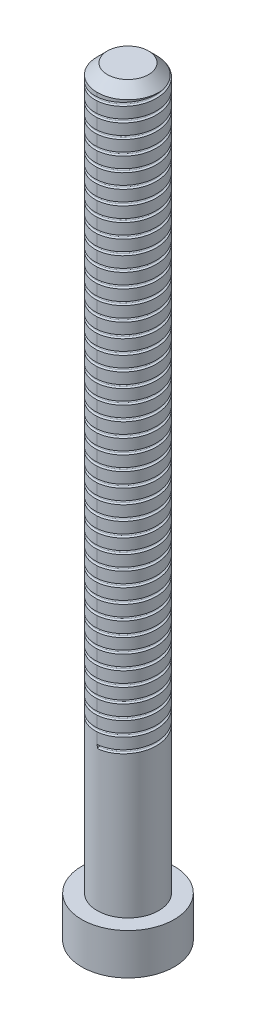
SolidWorks part; units mm, degrees
note: '?' marks a value the reader was unsure of.
ref_plane "Front Plane" through (0, 0, 0) normal (0, 0, 1) x (1, 0, 0)
ref_plane "Top Plane" through (0, 0, 0) normal (0, 1, 0) x (1, 0, 0)
ref_plane "Right Plane" through (0, 0, 0) normal (1, 0, 0) x (0, 0, -1)
sketch "Sketch1" plane through (0, 0, 0) normal (0, 1, 0) x (1, 0, 0)
  line L1 (2.5981, 0) -> (1.299, 2.25) construction
  line L2 (1.299, 2.25) -> (-1.299, 2.25) construction
  line L3 (-1.299, 2.25) -> (-2.5981, 0) construction
  line L4 (-2.5981, 0) -> (-1.299, -2.25) construction
  line L5 (-1.299, -2.25) -> (1.299, -2.25) construction
  line L6 (1.299, -2.25) -> (2.5981, 0) construction
  circle A0 centre (0, 0) radius 2.25
  dimension "D1" = 4.5
extrude "Boss-Extrude1" add sketch "Sketch1" along normal blind 37
sketch "Sketch2" plane through (0, 37, 0) normal (0, 1, 0) x (1, 0, 0)
  circle A0 centre (0, 0) radius 1.5
  dimension "D1" = 3
extrude "Cut-Extrude1" cut sketch "Sketch2" against normal blind 35 flip side to cut
ref_axis "Axis1" through (0, 2, 0) along (0, 1, 0)?
chamfer "Chamfer1" distance 0.5 angle 45 1 edges at (0, 37, 1.5)
sketch "Sketch5" plane through (0, 37, 0) normal (0, 1, 0) x (1, 0, 0)
  circle A0 centre (0, 0) radius 1.5
  dimension "D1" = 3
curve "Helix/Spiral1" pitch 0.7 height 28 turns 40
ref_plane "Plane1" through (0, 37, 1.5) normal (-0.9973, -0.0741, 0) x (0, 0, 1)
sketch "Sketch7" plane through (0, 37, 1.5) normal (-0.9973, -0.0741, 0) x (0, 0, 1)
  line L0 (-0.081, -0.0303) -> (0.549, 0.2747)
  line L1 (0.549, 0.2747) -> (0.549, -0.4253)
  line L2 (0.549, -0.4253) -> (-0.081, -0.1203)
  arc A0 (-0.081, -0.0303) -> (-0.081, -0.1203) centre (-0.0592, -0.0753) ccw
  dimension "D2" = 0.05
  dimension "D1" = 0.7
sweep "Cut-Sweep1" cut profiles "Sketch7" path "Helix/Spiral1"
sketch "Sketch8" plane through (0, 0, 0) normal (0, -1, 0) x (1, 0, 0)
  line L1 (1.1547, 0) -> (0.5774, 1)
  line L2 (0.5774, 1) -> (-0.5774, 1)
  line L3 (-0.5774, 1) -> (-1.1547, 0)
  line L4 (-1.1547, 0) -> (-0.5774, -1)
  line L5 (-0.5774, -1) -> (0.5774, -1)
  line L6 (0.5774, -1) -> (1.1547, 0)
  circle A0 centre (0, 0) radius 1 construction
  dimension "D1" = 2
extrude "Cut-Extrude2" cut sketch "Sketch8" against normal blind 1.5
